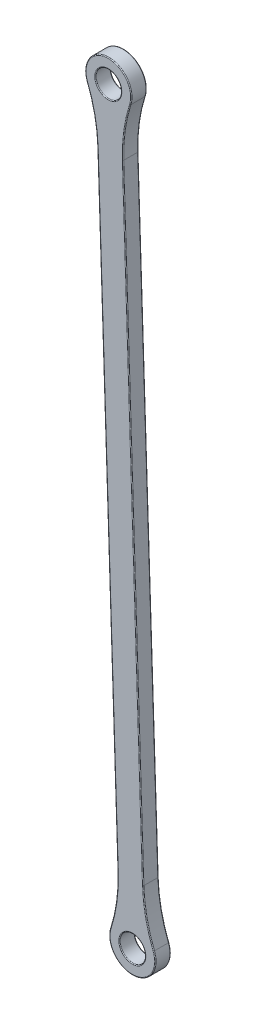
SolidWorks part; units mm, degrees
ref_plane "Front Plane" through (0, 0, 0) normal (0, 0, 1) x (1, 0, 0)
ref_plane "Top Plane" through (0, 0, 0) normal (0, 1, 0) x (1, 0, 0)
ref_plane "Right Plane" through (0, 0, 0) normal (1, 0, 0) x (0, 0, -1)
sketch "Sketch1" plane through (0, 0, 0) normal (0, 0, 1) x (1, 0, 0)
  line L0 (12.5011, 81.4348) -> (7.8087, 225.3057) construction
  line L1 (12.5011, 81.4348) -> (7.8087, 225.3057) construction
  line L2 (12.5011, 81.4348) -> (7.8087, 225.3057) construction
  line L3 (10.0024, 81.3533) -> (5.31, 225.2242)
  line L4 (14.9997, 81.5163) -> (10.3073, 225.3872)
  circle A0 centre (7.8087, 225.3057) radius 4.5 construction
  circle A1 centre (12.5011, 81.4348) radius 4.5 construction
  arc A2 (10.0024, 81.3533) -> (14.9997, 81.5163) centre (12.5011, 81.4348) ccw
  arc A3 (10.3073, 225.3872) -> (5.31, 225.2242) centre (7.8087, 225.3057) ccw
  arc A4 (5.31, 225.2242) -> (10.3073, 225.3872) centre (7.8087, 225.3057) ccw
  arc A5 (10.0024, 81.3533) -> (14.9997, 81.5163) centre (12.5011, 81.4348) cw
  arc A6 (5.432, 221.4846) -> (10.4293, 221.6476) centre (7.8087, 225.3057) cw
  arc A7 (9.8804, 85.093) -> (14.8778, 85.256) centre (12.5011, 81.4348) ccw
  point P5 (10.1549, 153.3703)
  dimension "D1" = 9
  dimension "D2" = 5
extrude "Boss-Extrude1" add sketch "Sketch1" against normal blind 3 contours A6 L3 A3 L4 | L3 A5 L4 A4 | L3 A7 L4 A2 region at (12.5866, 78.8136, 0) region at (10.1549, 153.3703, 0) region at (7.666, 229.6808, 0)
fillet "Fillet1" radius 30 4 edges at (5.432, 221.4846, -1.5) (10.4293, 221.6476, -1.5) (9.8804, 85.093, -1.5) (14.8778, 85.256, -1.5)
fillet "Fillet2" radius 0.15 20 edges at (15.0011, 81.4348, 0) (5.0831, 218.7451, 0) (7.662, 229.8033, 0) (10.9559, 218.9366, 0) (12.6535, 153.4518, 0) (15.2266, 87.9954, 0) (12.6478, 76.9372, 0) (9.3538, 87.8039, 0) (7.6562, 153.2888, 0) (10.3087, 225.3057, 0) (10.3087, 225.3057, -3) (15.0011, 81.4348, -3) (7.6562, 153.2888, -3) (9.3538, 87.8039, -3) (12.6478, 76.9372, -3) (15.2266, 87.9954, -3) (12.6535, 153.4518, -3) (5.0831, 218.7451, -3) (10.9559, 218.9366, -3) (7.662, 229.8033, -3)
